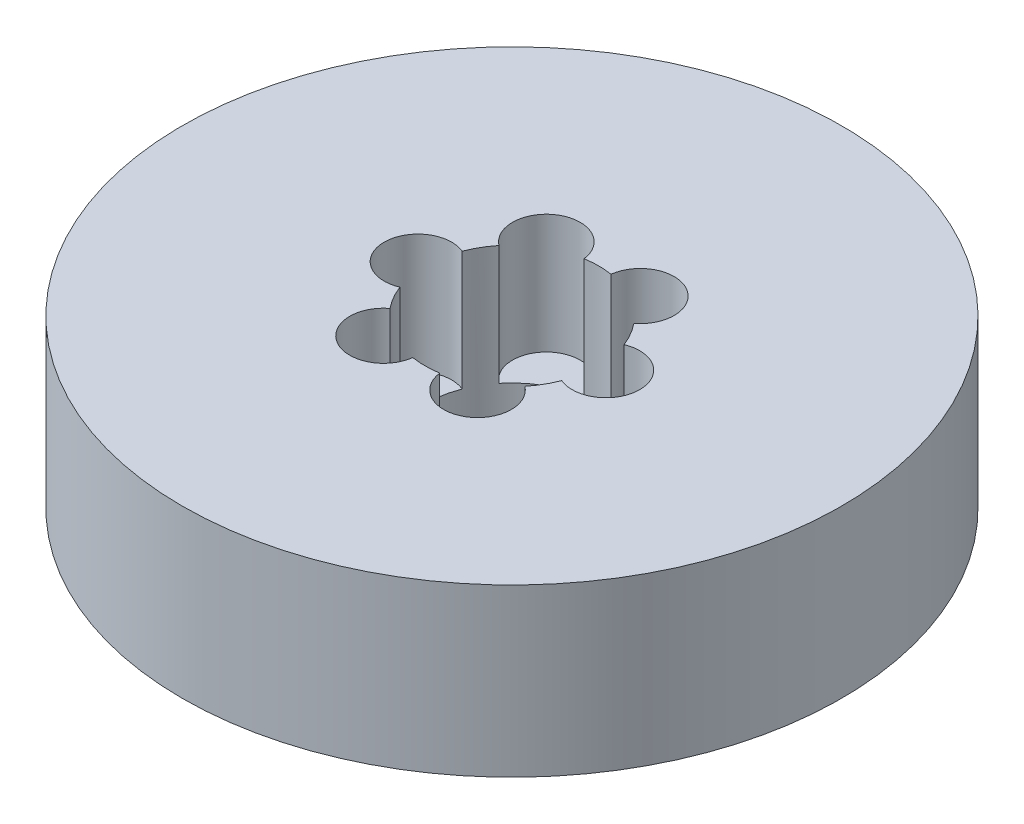
SolidWorks part; units mm, degrees
ref_plane "Front Plane" through (0, 0, 0) normal (0, 0, 1) x (1, 0, 0)
ref_plane "Top Plane" through (0, 0, 0) normal (0, 1, 0) x (1, 0, 0)
ref_plane "Right Plane" through (0, 0, 0) normal (1, 0, 0) x (0, 0, -1)
sketch "Sketch1" plane through (0, 0, 0) normal (0, 1, 0) x (1, 0, 0)
  circle A0 centre (0, 0) radius 47.5
  dimension "FLANGE_OD" = 95
extrude "Boss-Extrude1" add sketch "Sketch1" along normal blind 24
sketch "Sketch2" plane through (0, 0, 0) normal (0, 1, 0) x (1, 0, 0)
  circle A0 centre (0, 0) radius 12.5
  dimension "BORE_D" = 25
extrude "Cut-Extrude1" cut sketch "Sketch2" along normal through all
sketch "Sketch3" plane through (0, 24, 0) normal (0, 1, 0) x (1, 0, 0)
  circle A0 centre (0, 0) radius 13.5468 construction
  circle A1 centre (-13.5468, 0) radius 4.8721
  dimension "BOLT_D" = 9.7442
  dimension "BOLT_PCD" = 27.0937
extrude "Cut-Extrude2" cut sketch "Sketch3" against normal blind 17.2045
pattern_circular "CirPattern1" count 6 over 360 about axis through (0, 0, 0) along (0, 1, 0) of "Cut-Extrude2"
